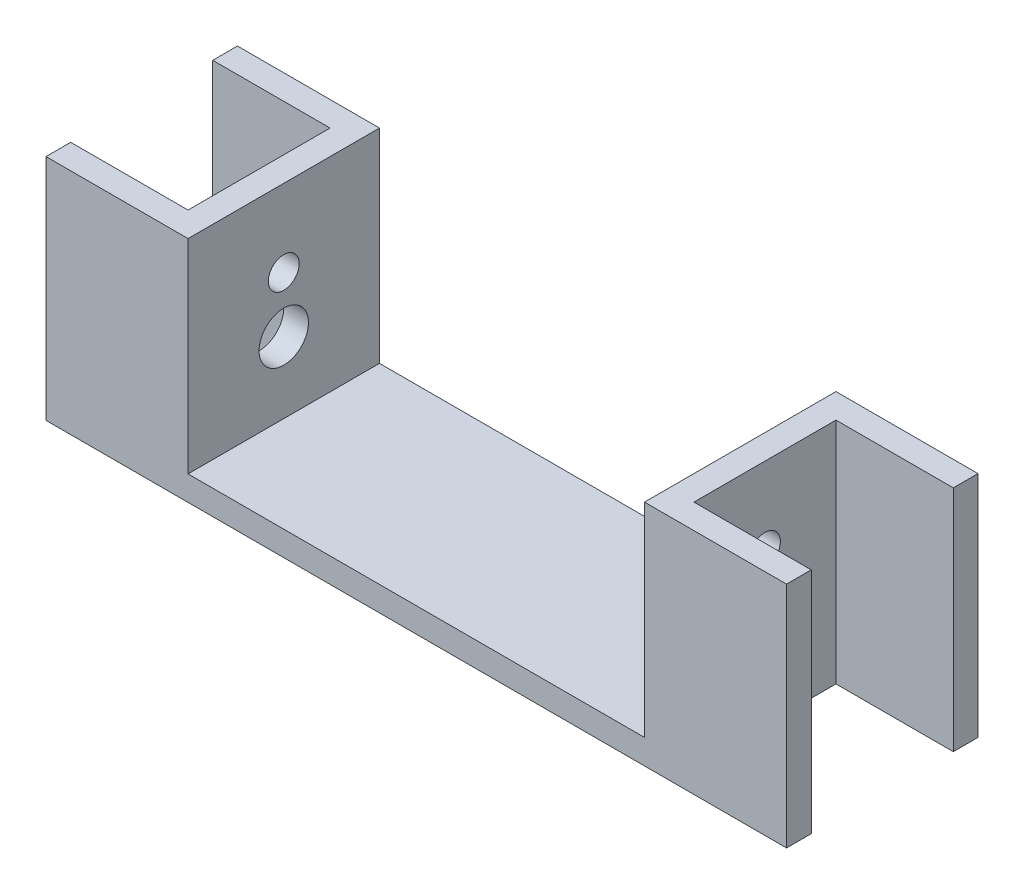
SolidWorks part; units mm, degrees
ref_plane "Front Plane" through (0, 0, 0) normal (0, 0, 1) x (1, 0, 0)
ref_plane "Top Plane" through (0, 0, 0) normal (0, 1, 0) x (1, 0, 0)
ref_plane "Right Plane" through (0, 0, 0) normal (1, 0, 0) x (0, 0, -1)
sketch "Sketch1" plane through (0, 0, 0) normal (0, 1, 0) x (1, 0, 0)
  line L0 (40.9555, 11.5) -> (59.9555, 11.5)
  line L1 (-59.9555, -15.5) -> (59.9555, -15.5)
  line L2 (-59.9555, -15.5) -> (-59.9555, -11.5)
  line L3 (-59.9555, 15.5) -> (59.9555, 15.5)
  line L4 (59.9555, -15.5) -> (59.9555, -11.5)
  line L5 (-59.9555, -15.5) -> (59.9555, 15.5) construction
  line L6 (-59.9555, 15.5) -> (59.9555, -15.5) construction
  line L8 (-40.9555, -11.5) -> (-40.9555, 11.5)
  line L10 (40.9555, -11.5) -> (40.9555, 11.5)
  line L11 (-40.9555, -11.5) -> (40.9555, 11.5) construction
  line L12 (-40.9555, 11.5) -> (40.9555, -11.5) construction
  line L14 (59.9555, -11.5) -> (40.9555, -11.5)
  line L15 (-40.9555, -11.5) -> (-59.9555, -11.5)
  line L16 (59.9555, 11.5) -> (59.9555, 15.5)
  line L17 (-59.9555, 11.5) -> (-40.9555, 11.5)
  line L18 (-59.9555, 11.5) -> (-59.9555, 15.5)
  point P0 (0, 0)
  point P6 (0, 0)
  dimension "D1" = 23
  dimension "D2" = 19
  dimension "D3" = 4
extrude "Boss-Extrude1" add sketch "Sketch1" along normal blind 4
sketch "Sketch2" plane through (0, 4, 0) normal (0, 1, 0) x (1, 0, 0)
  line L12 (-36.9555, 15.5) -> (-59.9555, 15.5)
  line L14 (-36.9555, -15.5) -> (-36.9555, 15.5)
  line L16 (36.9555, -15.5) -> (36.9555, 15.5)
  line L17 (-36.9555, -15.5) -> (36.9555, 15.5) construction
  line L18 (-36.9555, 15.5) -> (36.9555, -15.5) construction
  line L19 (36.9555, -15.5) -> (59.9555, -15.5)
  line L24 (59.9555, 11.5) -> (59.9555, 15.5)
  line L25 (59.9555, 15.5) -> (-59.9555, 15.5)
  line L26 (-59.9555, 15.5) -> (-59.9555, 11.5)
  line L27 (-59.9555, 11.5) -> (-40.9555, 11.5)
  line L28 (-40.9555, 11.5) -> (-40.9555, -11.5)
  line L29 (-40.9555, -11.5) -> (-59.9555, -11.5)
  line L30 (-59.9555, -11.5) -> (-59.9555, -15.5)
  line L31 (-59.9555, -15.5) -> (59.9555, -15.5)
  line L32 (59.9555, -15.5) -> (59.9555, -11.5)
  line L33 (59.9555, -11.5) -> (40.9555, -11.5)
  line L34 (40.9555, -11.5) -> (40.9555, 11.5)
  line L35 (40.9555, 11.5) -> (59.9555, 11.5)
  line L36 (59.9555, 11.5) -> (59.9555, 15.5)
  line L37 (59.9555, 15.5) -> (36.9555, 15.5)
  line L38 (-59.9555, 15.5) -> (-59.9555, 11.5)
  line L39 (-59.9555, 11.5) -> (-40.9555, 11.5)
  line L40 (-40.9555, 11.5) -> (-40.9555, -11.5)
  line L41 (-40.9555, -11.5) -> (-59.9555, -11.5)
  line L42 (-59.9555, -11.5) -> (-59.9555, -15.5)
  line L43 (-59.9555, -15.5) -> (-36.9555, -15.5)
  line L44 (59.9555, -15.5) -> (59.9555, -11.5)
  line L45 (59.9555, -11.5) -> (40.9555, -11.5)
  line L46 (40.9555, -11.5) -> (40.9555, 11.5)
  line L47 (40.9555, 11.5) -> (59.9555, 11.5)
  point P2 (0, 0)
  dimension "D2" = 4
  dimension "D1" = 0
extrude "Boss-Extrude2" add sketch "Sketch2" along normal blind 37 from surface starting at face at (0, 0, 0)
sketch "Sketch3" plane through (-40.9555, 0, 0) normal (-1, 0, 0) x (0, 0, 1)
  line L0 (0, 37) -> (0, 0) construction
  line L1 (11.5, 37) -> (-11.5, 37) construction
  line L2 (-11.5, 0) -> (11.5, 0) construction
  circle A0 centre (0, 15.5) radius 4
  circle A1 centre (0, 24.5) radius 2.5
  dimension "D1" = 8
  dimension "D2" = 5
  dimension "D3" = 15.5
  dimension "D4" = 24.5
extrude "Cut-Extrude1" cut sketch "Sketch3" against normal through all
